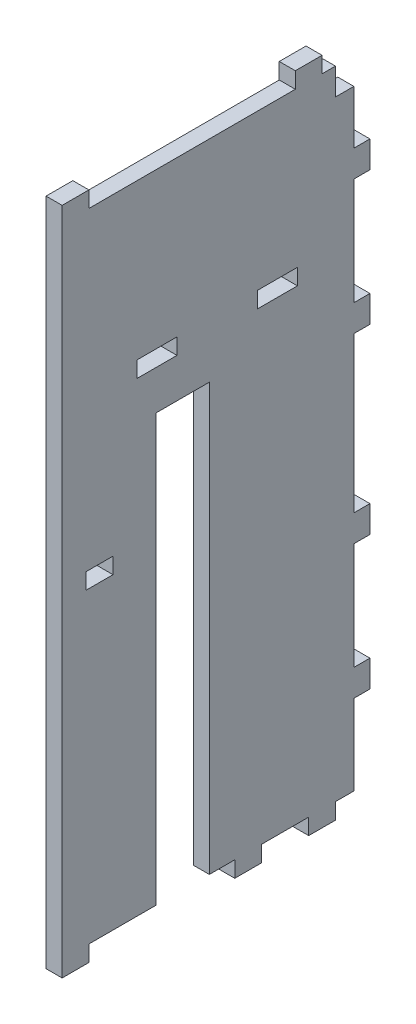
SolidWorks part; units mm, degrees
ref_plane "Plan de face" through (0, 0, 0) normal (0, 0, 1) x (1, 0, 0)
ref_plane "Plan de dessus" through (0, 0, 0) normal (0, 1, 0) x (1, 0, 0)
ref_plane "Plan de droite" through (0, 0, 0) normal (1, 0, 0) x (0, 0, -1)
sketch "Esquisse1" plane through (0, 0, 0) normal (1, 0, 0) x (0, 0, -1)
  line L0 (97.1531, 0) -> (-102.2664, 0) construction
  line L1 (-54.5, 119) -> (54.5, 119)
  line L2 (-54.5, 119) -> (-54.5, -119)
  line L3 (-54.5, -119) -> (54.5, -119)
  line L4 (54.5, 119) -> (54.5, -119)
  line L5 (0, 172.7153) -> (0, -236.1933) construction
  line L7 (-45.5, -4) -> (-35.5, -4)
  line L8 (-45.5, -4) -> (-45.5, 2)
  line L9 (-45.5, 2) -> (-35.5, 2)
  line L10 (-35.5, -4) -> (-35.5, 2)
  line L15 (-26.585, 61) -> (-11.585, 61)
  line L16 (-26.585, 61) -> (-26.585, 55)
  line L17 (-26.585, 55) -> (-11.585, 55)
  line L18 (-11.585, 61) -> (-11.585, 55)
  line L19 (18.415, 61) -> (33.415, 61)
  line L20 (18.415, 61) -> (18.415, 55)
  line L21 (18.415, 55) -> (33.415, 55)
  line L22 (33.415, 61) -> (33.415, 55)
  dimension "D1" = 238
  dimension "D2" = 109
  dimension "D4" = 119
  dimension "D13" = 15
  dimension "D14" = 15
  dimension "D15" = 30
  dimension "D16" = 6
  dimension "D17" = 6
  dimension "D3" = 54.5
  dimension "D5" = 58
  dimension "D6" = 27.915
  dimension "D7" = 10
  dimension "D8" = 6
  dimension "D9" = 9
  dimension "D10" = 117
extrude "Boss.-Extru.1" add sketch "Esquisse1" along normal blind 6
sketch "Esquisse3" plane through (6, 0, 0) normal (1, 0, 0) x (0, 0, -1)
  line L0 (-54.5, -119) -> (54.5, -119) construction
  line L1 (-54.5, -119) -> (-44.5, -119)
  line L2 (-54.5, -119) -> (-54.5, -125)
  line L3 (-54.5, -125) -> (-44.5, -125)
  line L4 (-44.5, -119) -> (-44.5, -125)
  line L5 (245.3741, 0) -> (-166.5298, 0) construction
  line L6 (54.5, -119) -> (54.5, 119) construction
  line L7 (37.62, -119) -> (47.62, -119)
  line L8 (37.62, -119) -> (37.62, -125)
  line L9 (37.62, -125) -> (47.62, -125)
  line L10 (0, 208.6671) -> (0, -232.3841) construction
  line L11 (-54.5, -119) -> (54.5, -119) construction
  line L12 (47.62, -119) -> (47.62, -125)
  line L13 (60.5, 39) -> (60.5, 29)
  line L14 (54.5, 29) -> (60.5, 29)
  line L15 (54.5, 39) -> (54.5, 29)
  line L16 (54.5, 39) -> (60.5, 39)
  line L17 (60.5, 89) -> (60.5, 79)
  line L18 (54.5, 79) -> (60.5, 79)
  line L19 (54.5, 89) -> (54.5, 79)
  line L20 (54.5, 89) -> (60.5, 89)
  line L21 (54.5, -119) -> (54.5, 119) construction
  line L22 (54.5, -89) -> (60.5, -89)
  line L23 (54.5, -89) -> (54.5, -79)
  line L24 (54.5, -79) -> (60.5, -79)
  line L25 (60.5, -89) -> (60.5, -79)
  line L26 (54.5, -39) -> (60.5, -39)
  line L27 (54.5, -39) -> (54.5, -29)
  line L28 (54.5, -29) -> (60.5, -29)
  line L29 (0, -208.6671) -> (0, 232.3841) construction
  line L30 (10, -119) -> (20, -119)
  line L31 (10, -119) -> (10, -125)
  line L32 (10, -125) -> (20, -125)
  line L33 (20, -119) -> (20, -125)
  line L34 (32.62, 119) -> (42.62, 119)
  line L35 (60.5, -39) -> (60.5, -29)
  line L36 (32.62, 119) -> (32.62, 125)
  line L37 (32.62, 125) -> (42.62, 125)
  line L38 (42.62, 119) -> (42.62, 125)
  line L50 (-44.5, 119) -> (-44.5, 125)
  line L51 (-54.5, 125) -> (-44.5, 125)
  line L52 (-54.5, 119) -> (-54.5, 125)
  line L53 (-54.5, 119) -> (-44.5, 119)
  dimension "D2" = 10
  dimension "D3" = 6
  dimension "D4" = 10
  dimension "D5" = 6.88
  dimension "D6" = 6
  dimension "D7" = 6
  dimension "D8" = 10
  dimension "D9" = 6
  dimension "D10" = 10
  dimension "D11" = 6
  dimension "D12" = 10
  dimension "D13" = 17.62
  dimension "D14" = 30
  dimension "D15" = 40
  dimension "D16" = 6
  dimension "D17" = 10
  dimension "D18" = 11.88
extrude "Boss.-Extru.5" add sketch "Esquisse3" against normal blind 6
sketch "Esquisse6" plane through (6, 0, 0) normal (1, 0, 0) x (0, 0, -1)
  line L0 (-44.5, -119) -> (10, -119) construction
  line L1 (-19.5, -119) -> (0.5, -119)
  line L2 (-19.5, -119) -> (-19.5, 40.29)
  line L3 (-19.5, 40.29) -> (0.5, 40.29)
  line L4 (0.5, -119) -> (0.5, 40.29)
  line L5 (54.5, -79) -> (54.5, -39) construction
  line L6 (-44.5, 125) -> (-54.5, 125) construction
  dimension "D1" = 20
  dimension "D2" = 84.71
  dimension "D3" = 54
extrude "Enlèv. mat.-Extru.2" cut sketch "Esquisse6" against normal blind 6
sketch "Esquisse7" plane through (0, 0, 0) normal (-1, 0, 0) x (0, 0, 1)
  line L1 (-54.5, 119) -> (-47.62, 119)
  line L2 (-54.5, 119) -> (-54.5, 109)
  line L3 (-54.5, 109) -> (-47.62, 109)
  line L4 (-47.62, 119) -> (-47.62, 109)
  dimension "D1" = 10
  dimension "D2" = 6.88
extrude "Enlèv. mat.-Extru.3" cut sketch "Esquisse7" against normal blind 6
equation "\"D3@Esquisse1\"=\"D2@Esquisse1\"/2"
equation "\"D4@Esquisse1\"=\"D1@Esquisse1\"/2"
